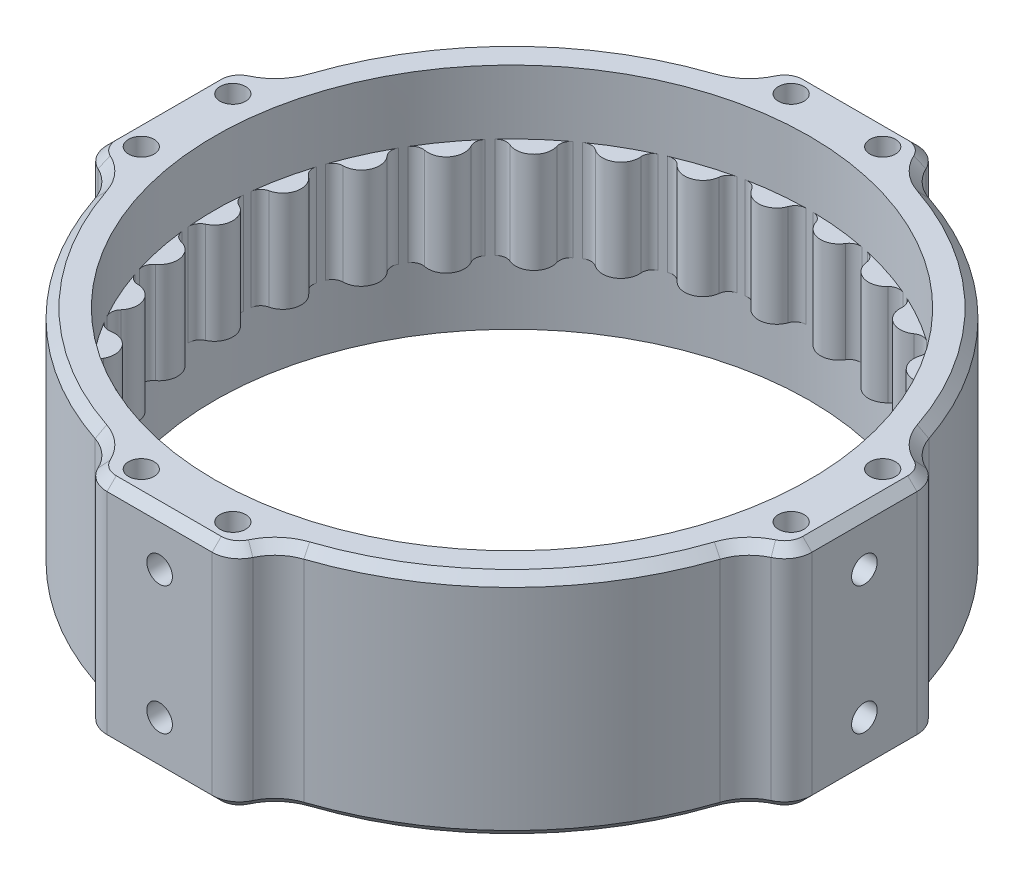
SolidWorks part; units mm, degrees
material "Like ABS"
ref_plane "Front Plane" through (0, 0, 0) normal (0, 0, 1) x (1, 0, 0)
ref_plane "Top Plane" through (0, 0, 0) normal (0, 1, 0) x (1, 0, 0)
ref_plane "Right Plane" through (0, 0, 0) normal (1, 0, 0) x (0, 0, -1)
sketch "Sketch6" plane through (0, 0, 0) normal (0, 1, 0) x (1, 0, 0)
  circle A0 centre (0, 0) radius 32.5
  circle A1 centre (0, 0) radius 36
  dimension "D1" = 65
  dimension "D2" = 72
extrude "Boss-Extrude10" add sketch "Sketch6" along normal blind 11
sketch "Sketch7" plane through (0, 11, 0) normal (0, 1, 0) x (1, 0, 0)
  circle A0 centre (-32.5, 0) radius 2
  circle A1 centre (0, 0) radius 32.5 construction
  dimension "D1" = 4
extrude "Boss-Extrude11" add sketch "Sketch7" against normal up to surface (11 mm away) up to face at (0, 0, 36)
fillet "Fillet2" radius 1.2 2 edges at (-32.4385, 5.5, -1.9991) (-32.4385, 5.5, 1.9991)
pattern_circular "CirPattern2" count 30 over 360 about axis through (0, 11, 0) along (0, 1, 0) of "Fillet2", "Boss-Extrude11"
sketch "Sketch8" plane through (0, 11, 0) normal (0, 1, 0) x (1, 0, 0)
  circle A0 centre (0, 0) radius 36
  circle A1 centre (0, 0) radius 32.5
  dimension "D1" = 72
  dimension "D2" = 65
extrude "Boss-Extrude12" add sketch "Sketch8" along normal blind 7
sketch "Sketch9" plane through (0, 0, 0) normal (0, -1, 0) x (1, 0, 0)
  circle A0 centre (0, 0) radius 32.5
  circle A1 centre (0, 0) radius 36
  dimension "D1" = 72
  dimension "D2" = 65
extrude "Boss-Extrude13" add sketch "Sketch9" along normal blind 7
sketch "Sketch10" plane through (0, 18, 0) normal (0, 1, 0) x (1, 0, 0)
  line L0 (0, 0) -> (-32.5, 0) construction
  line L1 (-32.5, 0) -> (-38.5, 0) construction
  line L2 (-38.5, 0) -> (-38.5, 5) construction
  line L3 (-38.5, 5) -> (-38.5, 8) construction
  line L5 (-38.5, 8) -> (-33.5607, 8)
  line L6 (-38.5, 8) -> (-38.5, -8)
  line L7 (-38.5, -8) -> (-33.5607, -8)
  line L8 (-33.5607, 8) -> (-33.5607, -8)
  arc A0 (-32.3594, 3.0195) -> (-32.3594, -3.0195) centre (0, 0) ccw construction
  dimension "D1" = 6
  dimension "D2" = 5
  dimension "D3" = 3
  dimension "D4" = 16
extrude "Boss-Extrude14" add sketch "Sketch10" against normal up to surface (25 mm away) up to face at (0, -7, -36)
sketch "Sketch11" plane through (0, 18, 0) normal (0, 1, 0) x (1, 0, 0)
  line L0 (-38.5, 8) -> (-38.5, 5) construction
  line L1 (-38.5, 8) -> (-38.5, -8) construction
  line L2 (-38.5, 5) -> (-35.5, 5) construction
  line L3 (-35.5, 5) -> (-35.5, -5) construction
  line L4 (-35.5, -5) -> (-35.5, -8) construction
  line L5 (-38.5, -8) -> (-35.0999, -8) construction
  circle A0 centre (-35.5, 5) radius 1.4
  circle A1 centre (-35.5, -5) radius 1.4
  dimension "D3" = 2.8
  dimension "D1" = 3
  dimension "D2" = 3
extrude "Cut-Extrude1" cut sketch "Sketch11" against normal up to surface (25 mm away) up to face at (-19.025, -7, 0)
sketch "Sketch12" plane through (-38.5, 0, 0) normal (-1, 0, 0) x (0, 0, 1)
  line L0 (0, -7) -> (0, -1.5) construction
  line L1 (-8, -7) -> (8, -7) construction
  line L2 (0, -1.5) -> (0, 12.5) construction
  line L3 (0, 12.5) -> (0, 18) construction
  line L4 (-8, 18) -> (8, 18) construction
  circle A0 centre (0, 12.5) radius 1.4
  circle A1 centre (0, -1.5) radius 1.4
  dimension "D2" = 2.8
  dimension "D1" = 14
extrude "Cut-Extrude2" cut sketch "Sketch12" against normal blind 4
fillet "Fillet3" radius 5 2 edges at (-35.0999, 5.5, -8) (-35.0999, 5.5, 8)
fillet "Fillet4" radius 3 2 edges at (-38.5, 5.5, -8) (-38.5, 5.5, 8)
pattern_circular "CirPattern3" count 4 over 360 about axis through (0, 11, 0) along (0, -1, 0) of "Fillet4", "Fillet3", "Cut-Extrude2", "Cut-Extrude1", "Boss-Extrude14"
chamfer "Chamfer1" distance 1 angle 45 14 edges at (-35.1562, -7, 9.6588) (-38.0311, -7, 7.3487) (-38.5, -7, 0) (-38.0311, -7, -7.3487) (-35.1562, -7, -9.6588) (-25.4558, -7, -25.4558) (25.4558, 18, 25.4558) (25.4558, 18, -25.4558) (-25.4558, 18, 25.4558) (-35.1562, 18, 9.6588) (-38.0311, 18, 7.3487) (-38.5, 18, 0) (-38.0311, 18, -7.3487) (-35.1562, 18, -9.6588)
